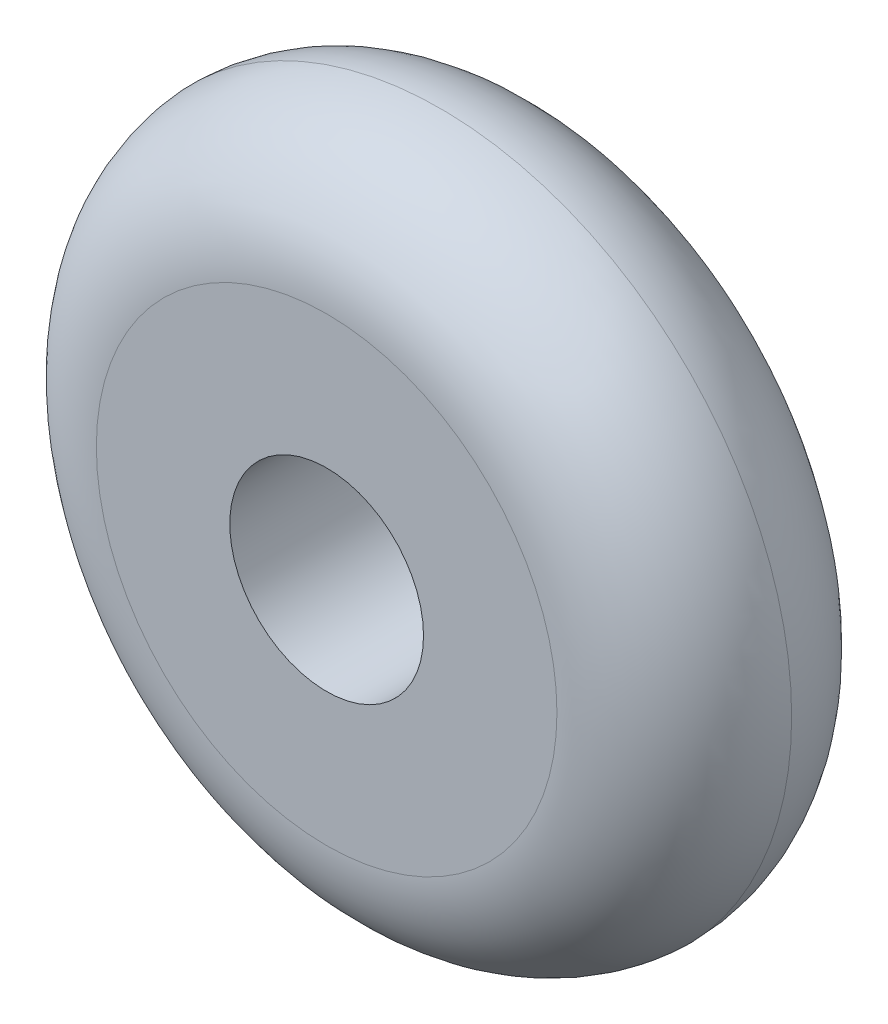
SolidWorks part; units mm, degrees
ref_plane "Front Plane" through (0, 0, 0) normal (0, 0, 1) x (1, 0, 0)
ref_plane "Top Plane" through (0, 0, 0) normal (0, 1, 0) x (1, 0, 0)
ref_plane "Right Plane" through (0, 0, 0) normal (1, 0, 0) x (0, 0, -1)
sketch "Sketch1" plane through (0, 0, 0) normal (0, 0, 1) x (1, 0, 0)
  circle A0 centre (0, 0) radius 14.5
  circle A1 centre (0, 0) radius 4
  circle A2 centre (0, 0) radius 5
  circle A3 centre (0, 0) radius 10
  dimension "D1" = 29
  dimension "D2" = 8
  dimension "D3" = 10
  dimension "D4" = 20
extrude "Boss-Extrude1" add sketch "Sketch1" along normal blind 9.7 contours A0 | A1
fillet "Fillet1" radius 5 1 edges at (14.5, 0, 0)
fillet "Fillet2" radius 5 1 edges at (14.5, 0, 9.7)
